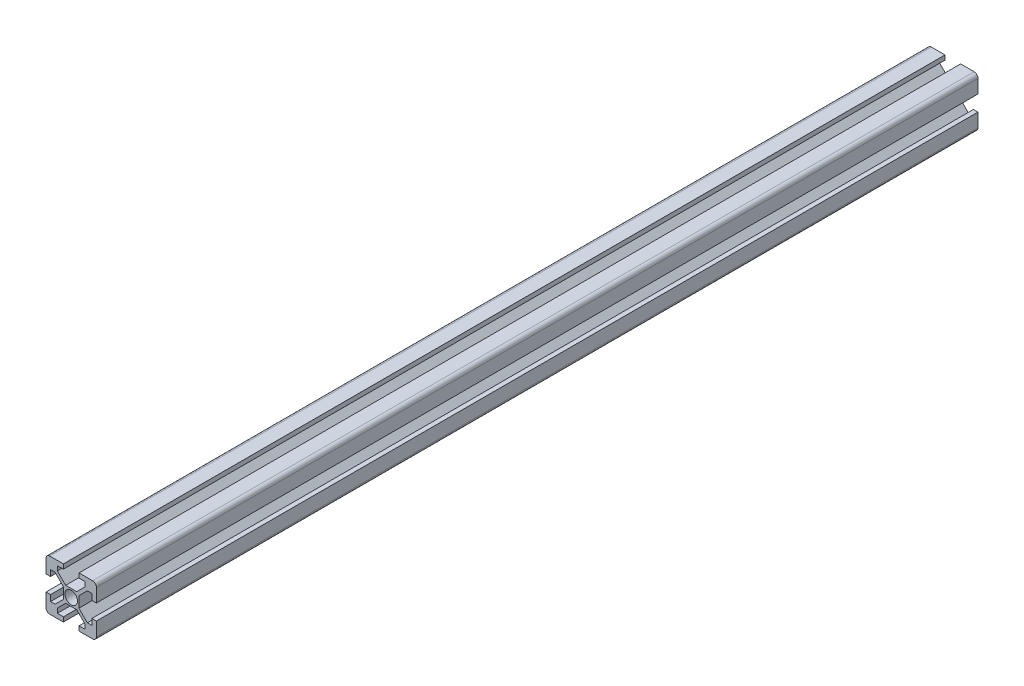
SolidWorks part; units mm, degrees
ref_plane "前视基准面" through (0, 0, 0) normal (0, 0, 1) x (1, 0, 0)
ref_plane "上视基准面" through (0, 0, 0) normal (0, 1, 0) x (1, 0, 0)
ref_plane "右视基准面" through (0, 0, 0) normal (1, 0, 0) x (0, 0, -1)
sketch "草图1" plane through (0, 0, 0) normal (0, 0, 1) x (1, 0, 0)
  line L0 (-10, -3.1) -> (-8.2, -3.1)
  line L1 (-8.5, 10) -> (8.5, 10)
  line L2 (-10, 8.5) -> (-10, -8.5)
  line L3 (-8.5, -10) -> (8.5, -10)
  line L4 (10, 8.5) -> (10, -8.5)
  line L5 (-10, 10) -> (10, -10) construction
  line L6 (-10, -10) -> (10, 10) construction
  line L7 (-3.0541, 3.1) -> (3.0541, 3.1)
  line L8 (-3.0541, 3.1) -> (-3.0541, -3.1)
  line L9 (-3.0541, -3.1) -> (3.0541, -3.1)
  line L10 (3.0541, 3.1) -> (3.0541, -3.1)
  line L11 (-3.0541, 3.1) -> (3.0541, -3.1) construction
  line L12 (-3.0541, -3.1) -> (3.0541, 3.1) construction
  line L13 (-8.2, -3.1) -> (-8.2, -5.5)
  line L14 (-8.2, -5.5) -> (-6.3971, -5.5)
  line L15 (-6.3971, -5.5) -> (-3.0541, -2.1571)
  line L16 (-5.5, 6.3971) -> (-2.1571, 3.0541)
  line L17 (-5.5, 8.2) -> (-5.5, 6.3971)
  line L18 (-3.1, 8.2) -> (-5.5, 8.2)
  line L19 (-3.1, 10) -> (-3.1, 8.2)
  line L20 (6.3971, 5.5) -> (3.0541, 2.1571)
  line L21 (8.2, 5.5) -> (6.3971, 5.5)
  line L22 (8.2, 3.1) -> (8.2, 5.5)
  line L23 (10, 3.1) -> (8.2, 3.1)
  line L24 (5.5, -6.3971) -> (2.1571, -3.0541)
  line L25 (5.5, -8.2) -> (5.5, -6.3971)
  line L26 (3.1, -8.2) -> (5.5, -8.2)
  line L27 (3.1, -10) -> (3.1, -8.2)
  line L28 (-3.1, -10) -> (-3.1, -8.2)
  line L29 (-3.1, -8.2) -> (-5.5, -8.2)
  line L30 (-5.5, -8.2) -> (-5.5, -6.3971)
  line L31 (-5.5, -6.3971) -> (-2.1571, -3.0541)
  line L32 (-8.2, 5.5) -> (-6.3971, 5.5)
  line L33 (-6.3971, 5.5) -> (-3.0541, 2.1571)
  line L34 (-8.2, 3.1) -> (-8.2, 5.5)
  line L35 (-10, 3.1) -> (-8.2, 3.1)
  line L36 (5.5, 8.2) -> (5.5, 6.3971)
  line L37 (5.5, 6.3971) -> (2.1571, 3.0541)
  line L38 (3.1, 8.2) -> (5.5, 8.2)
  line L39 (3.1, 10) -> (3.1, 8.2)
  line L40 (8.2, -5.5) -> (6.3971, -5.5)
  line L41 (6.3971, -5.5) -> (3.0541, -2.1571)
  line L42 (8.2, -3.1) -> (8.2, -5.5)
  line L43 (10, -3.1) -> (8.2, -3.1)
  circle A0 centre (0, 0) radius 2.5
  arc A1 (-10, 8.5) -> (-8.5, 10) centre (-8.5, 8.5) cw
  arc A2 (-10, -8.5) -> (-8.5, -10) centre (-8.5, -8.5) ccw
  arc A3 (8.5, 10) -> (10, 8.5) centre (8.5, 8.5) cw
  arc A4 (10, -8.5) -> (8.5, -10) centre (8.5, -8.5) cw
  point P0 (0, 0)
  point P20 (0, 0)
  point P26 (0, 0)
  point P32 (0, 0)
  point P38 (0, 0)
  point P60 (0, 0)
  dimension "D1" = 4
  dimension "D3" = 1.5
  dimension "D4" = 1.5
  dimension "D5" = 1.5
  dimension "D2" = 4
extrude "凸台-拉伸1" add sketch "草图1" along normal blind 350 contours A1 L2 L35 L34 L32 L33 L8 L7 L16 L17 L18 L19 L1 | A3 L1 L39 L38 L36 L37 L7 L10 L20 L21 L22 L23 L4 | L10 L7 L8 L9 A0 | A4 L4 L43 L42 L40 L41 L10 L9 L24 L25 L26 L27 L3 | L2 A2 L3 L28 L29 L30 L31 L9 L8 L15 L14 L13 L0 region at (-6.9209, -6.9203, 0) region at (-6.9209, 6.9203, 0) region at (-2.9671, 0, 0) region at (6.9209, -6.9203, 0) region at (6.9209, 6.9203, 0)
